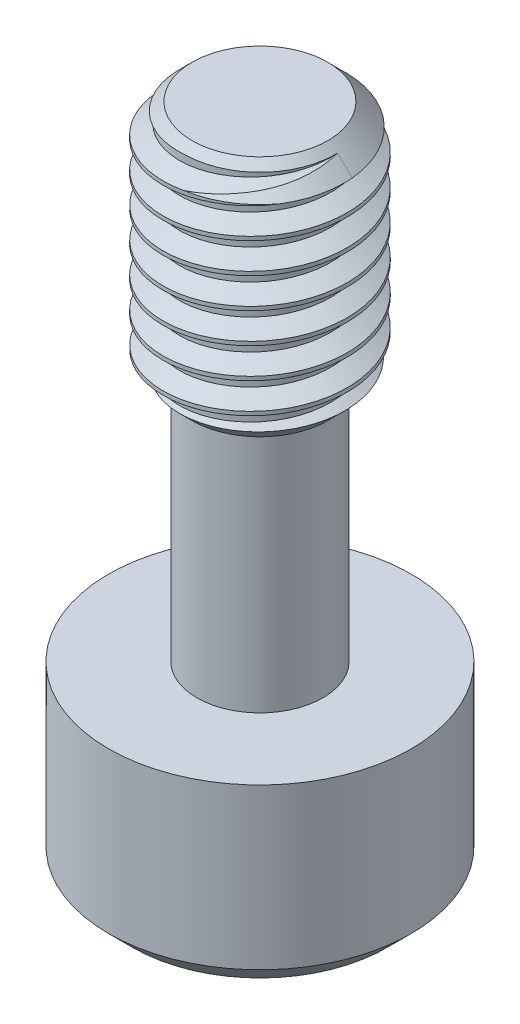
SolidWorks part; units mm, degrees
material "AISI 304"
ref_plane "Front Plane" through (0, 0, 0) normal (0, 0, 1) x (1, 0, 0)
ref_plane "Top Plane" through (0, 0, 0) normal (0, 1, 0) x (1, 0, 0)
ref_plane "Right Plane" through (0, 0, 0) normal (1, 0, 0) x (0, 0, -1)
sketch "Sketch1" plane through (0, 0, 0) normal (0, 1, 0) x (1, 0, 0)
  circle A0 centre (0, 0) radius 3.9624
  dimension "D1" = 7.9248
extrude "Boss-Extrude1" add sketch "Sketch1" along normal blind 4.826
sketch "Sketch2" plane through (0, 4.826, 0) normal (0, 1, 0) x (1, 0, 0)
  circle A0 centre (0, 0) radius 1.651
  dimension "D1" = 3.302
extrude "Boss-Extrude2" add sketch "Sketch2" along normal blind 6.35
sketch "Sketch3" plane through (0, 11.176, 0) normal (0, 1, 0) x (1, 0, 0)
  circle A0 centre (0, 0) radius 2.413
  dimension "D1" = 4.826
extrude "Boss-Extrude3" add sketch "Sketch3" along normal blind 6.35
chamfer "Chamfer1" distance 0.635 angle 45 1 edges at (0, 0, 3.9624)
chamfer "Chamfer3" distance 0.635 angle 45 2 edges at (0, 17.526, 2.413) (0, 11.176, 2.413)
sketch "Sketch9" plane through (0, 0, 0) normal (0, -1, 0) x (1, 0, 0)
  line L1 (2.3464, 0) -> (1.1732, 2.032)
  line L2 (1.1732, 2.032) -> (-1.1732, 2.032)
  line L3 (-1.1732, 2.032) -> (-2.3464, 0)
  line L4 (-2.3464, 0) -> (-1.1732, -2.032)
  line L5 (-1.1732, -2.032) -> (1.1732, -2.032)
  line L6 (1.1732, -2.032) -> (2.3464, 0)
  circle A0 centre (0, 0) radius 2.032 construction
  dimension "D1" = 4.064
extrude "Cut-Extrude2" cut sketch "Sketch9" against normal blind 2.54
thread "Thread1" pitch 0.7937 start angle 0, offset 1.27, length 0, pitch 0.7937, diameter 4.826
ref_plane "Plane1" through (-2.413, 18.161, 0) normal (0, 0, 1) x (-1, 0, 0)
sketch "Thread Profile1" plane through (-2.413, 18.161, 0) normal (0, 0, 1) x (-1, 0, 0)
  line L0 (0, 0) -> (0, 0.7937) construction
  line L11 (0, 0) -> (0, 0.6945)
  line L12 (0, 0.6945) -> (-0.4296, 0.4465)
  line L13 (-0.4296, 0.4465) -> (-0.4296, 0.248)
  line L15 (-0.4296, 0.248) -> (0, 0)
  line L17 (-0.4296, 0.3473) -> (0, 0.3473) construction
  point P2 (0, 0)
  dimension "Pitch" = 0.7937
  dimension "Profile_Angle" = 60
  dimension "Profile_Land" = 0.1984
  dimension "Profile_Height" = 0.4296
